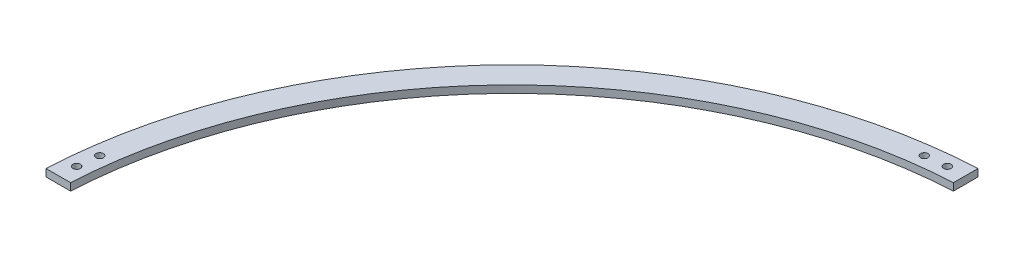
SolidWorks part; units mm, degrees
ref_plane "Front Plane" through (0, 0, 0) normal (0, 0, 1) x (1, 0, 0)
ref_plane "Top Plane" through (0, 0, 0) normal (0, 1, 0) x (1, 0, 0)
ref_plane "Right Plane" through (0, 0, 0) normal (1, 0, 0) x (0, 0, -1)
sketch "Sketch1" plane through (0, 0, 0) normal (0, 1, 0) x (1, 0, 0)
  line L1 (0, 200) -> (0, -200) construction
  line L6 (-200, 0) -> (200, 0) construction
  line L7 (-10, 199.7498) -> (-10, -199.7498) construction
  line L12 (-10, 199.7498) -> (-10, 189.7367)
  line L13 (-199.7498, 10) -> (199.7498, 10) construction
  line L14 (-199.7498, 10) -> (-189.7367, 10)
  arc A3 (-10, 199.7498) -> (-199.7498, 10) centre (0, 0) ccw
  arc A4 (-10, 189.7367) -> (-189.7367, 10) centre (0, 0) ccw
  arc A5 (-190, 0) -> (-189.7367, 10) centre (0, 0) ccw construction
  arc A6 (-200, 0) -> (-199.7498, 10) centre (0, 0) ccw construction
  circle A7 centre (0, 0) radius 195 construction
  dimension "D1" = 190
  dimension "D2" = 200
  dimension "D4" = 10
  dimension "D5" = 5
  dimension "D3" = 10
sketch "Sketch14" [suppressed] plane through (0, 0, 0) normal (0, 1, 0) x (1, 0, 0)
  line L0 (-200, 10) -> (200, 10) construction
  line L1 (-10, 200) -> (-10, -200) construction
  line L2 (-200, 10) -> (-189.7367, 10)
  line L3 (-10, 200) -> (-10, 189.7367)
  circle A0 centre (0, 0) radius 200 construction
  circle A1 centre (0, 0) radius 190 construction
  arc A2 (-10, 199.7498) -> (-199.7498, 10) centre (0, 0) ccw
  arc A3 (-10, 189.7367) -> (-189.7367, 10) centre (0, 0) ccw
sketch "roll" plane through (0, 0, 0) normal (0, 1, 0) x (1, 0, 0)
  line L0 (0, -195) -> (0, 195) construction
  dimension "D1" = 390
ref_axis "Axis1" through (0, -148.0362, 0) along (0, 1, 0)
extrude "base" add sketch "Sketch1" along normal mid plane 3 contours L14 A4 L12 A3
sketch "Sketch16" plane through (0, 1.5, 0) normal (0, 1, 0) x (1, 0, 0)
  line L0 (0, 200) -> (0, -200) construction
  line L1 (-200, 0) -> (200, 0) construction
  line L2 (0, 200) -> (0, -200) construction
  line L3 (-200, 0) -> (200, 0) construction
  line L4 (0, 0) -> (-194.258, 16.9954) construction
  line L5 (0, 0) -> (-193.3317, 25.4526) construction
  line L6 (0, 0) -> (-16.9954, 194.258) construction
  line L7 (0, 0) -> (-25.4526, 193.3317) construction
  circle A4 centre (0, 0) radius 195 construction
  circle A5 centre (0, 0) radius 195 construction
  dimension "D1" = 5
  dimension "D2" = 7.5
  dimension "D3" = 5
  dimension "D4" = 7.5
hole_wizard "Ø3.0 (3) Diameter Hole3" positions "Sketch20" profile "Sketch21" hole size "Ø3.0" standard "ISO" end condition through all
sketch "Sketch20" plane through (0, 1.5, 0) normal (0, 1, 0) x (1, 0, 0)
  point P0 (-194.258, 16.9954)
  point P3 (-193.3317, 25.4526)
  point P6 (-25.4526, 193.3317)
  point P9 (-16.9954, 194.258)
sketch "Sketch21" plane through (-194.258, 1.5, -16.9954) normal (1, 0, 0) x (0, 0, 1)
  line L0 (0, 0) -> (0, 3)
  line L1 (0, 3) -> (1.5, 3)
  line L2 (1.5, 3) -> (1.5, 0)
  line L5 (1.5, 0) -> (0, 0)
  line L11 (0, -6.35) -> (0, 107.95) construction
  dimension "Thru Hole Dia." = 3
  dimension "Thru Hole Depth" = 3
